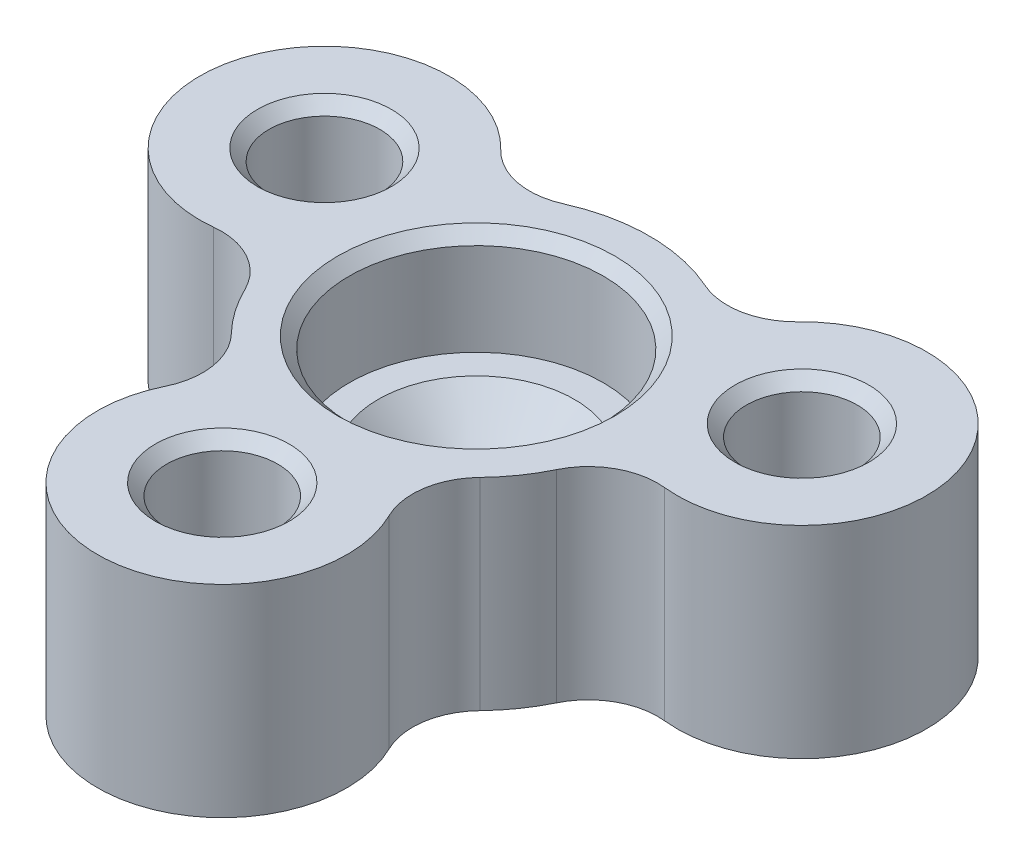
SolidWorks part; units mm, degrees
ref_plane "Plan de face" through (0, 0, 0) normal (0, 0, 1) x (1, 0, 0)
ref_plane "Plan de dessus" through (0, 0, 0) normal (0, 1, 0) x (1, 0, 0)
ref_plane "Plan de droite" through (0, 0, 0) normal (1, 0, 0) x (0, 0, -1)
sketch "Sketch1" plane through (0, 0, 0) normal (0, 1, 0) x (1, 0, 0)
  line L0 (0, 0) -> (0, -11) construction
  line L1 (0, 0) -> (-10.3366, 3.7622) construction
  line L2 (0, 0) -> (10.3366, 3.7622) construction
  circle A5 centre (0, 0) radius 5.5 construction
  circle A12 centre (0, -11) radius 2.4 construction
  arc A13 (-3.3074, -6.7314) -> (3.3074, -6.7314) centre (0, -11) ccw
  arc A14 (-7.4566, -0.8057) -> (-3.3074, -6.7314) centre (0, 0) ccw
  arc A19 (5.1942, 5.4102) -> (-5.1942, 5.4102) centre (0, 0) ccw
  arc A20 (3.3074, -6.7314) -> (7.4566, -0.8057) centre (0, 0) ccw
  circle A23 centre (0, -11) radius 1.7
  circle A24 centre (-10.3366, 3.7622) radius 1.7
  circle A25 centre (-10.3366, 3.7622) radius 2.4 construction
  arc A26 (-5.1942, 5.4102) -> (-7.4566, -0.8057) centre (-10.3366, 3.7622) ccw
  circle A27 centre (10.3366, 3.7622) radius 1.7
  circle A28 centre (10.3366, 3.7622) radius 2.4 construction
  arc A29 (7.4566, -0.8057) -> (5.1942, 5.4102) centre (10.3366, 3.7622) ccw
  point P14 (0, 0)
  point P20 (0, 0)
  point P21 (7.4566, -0.8057)
  point P22 (3.3074, -6.7314)
  point P23 (-3.3074, -6.7314)
  point P24 (-0.7399, -0.8057)
  point P25 (-7.4566, -0.8057)
  point P26 (0, 0)
  dimension "D1" = 2
  dimension "D4" = 3
  dimension "D2" = 11
  dimension "D3" = 4.8
  dimension "D6" = 110
  dimension "D7" = 3.4
  dimension "D5" = 11
  dimension "D8" = 110
extrude "Boss-Extrude1" add sketch "Sketch1" against normal blind 8.7483 contours A5 | A5 | A25 A24 | A12 A23 | A13 A20 A19 A14 A12 A25 region at (0, 0, 0.6749)
sketch "Esquisse3" plane through (0, 0, 0) normal (0, 1, 0) x (1, 0, 0)
  point P0 (-10.3366, 3.7622)
  point P3 (10.3366, 3.7622)
  point P6 (0, -11)
hole_wizard "Ø4.8 (4.8) Diameter Hole1" positions "Esquisse3" profile "Esquisse2" hole size "Ø4.8" standard "ANSI Metric"
sketch "Esquisse2" plane through (-10.3366, 0, -3.7622) normal (1, 0, 0) x (0, 0, 1)
  line L0 (0, 0) -> (0, 7.8421)
  line L1 (0, 7.8421) -> (2.4, 6.4)
  line L2 (2.4, 6.4) -> (2.4, 0)
  line L5 (2.4, 0) -> (0, 0)
  line L10 (0, 7.8421) -> (-2.4, 6.4) construction
  line L11 (0, -6.35) -> (0, 107.95) construction
  dimension "Hole Dia." = 4.8
  dimension "Hole Depth" = 6.4
  dimension "Drill Angle" = 118
chamfer "Chanfrein3" distance 0.5 angle 45 3 edges at (0, 0, 13.4) (10.3366, 0, -1.3622) (-10.3366, 0, -1.3622)
sketch "Sketch2" plane through (0, 0, 0) normal (1, 0, 0) x (0, 0, -1)
  line L0 (0, 1.699) -> (0, -5.7208) construction
  line L1 (0, 0) -> (6, 0)
  line L3 (5.5, -0.5) -> (5.5, -4.5)
  line L4 (5.5, -4.5) -> (4.25, -4.5)
  line L5 (4.25, -4.5) -> (4.25, -6.5)
  line L6 (4.25, -6.5) -> (0, -6.5)
  line L7 (0, -6.5) -> (0, 0)
  line L8 (5.5, -0.5) -> (6, 0)
  dimension "D1" = 4.25
  dimension "D2" = 2
  dimension "D3" = 4
  dimension "D4" = 0.5
  dimension "D5" = 45
  dimension "D6" = 5.5
revolve "Cut-Revolve1" cut sketch "Sketch2" angle 360 about L0
fillet "Fillet1" radius 3 6 edges at (-3.3074, -4.3741, 6.7314) (3.3074, -4.3741, 6.7314) (-7.4566, -4.3741, 0.8057) (-5.1942, -4.3741, -5.4102) (5.1942, -4.3741, -5.4102) (7.4566, -4.3741, 0.8057)
chamfer "Chanfrein2" distance 2 angle 45 1 edges at (0, -6.5, 4.25)
